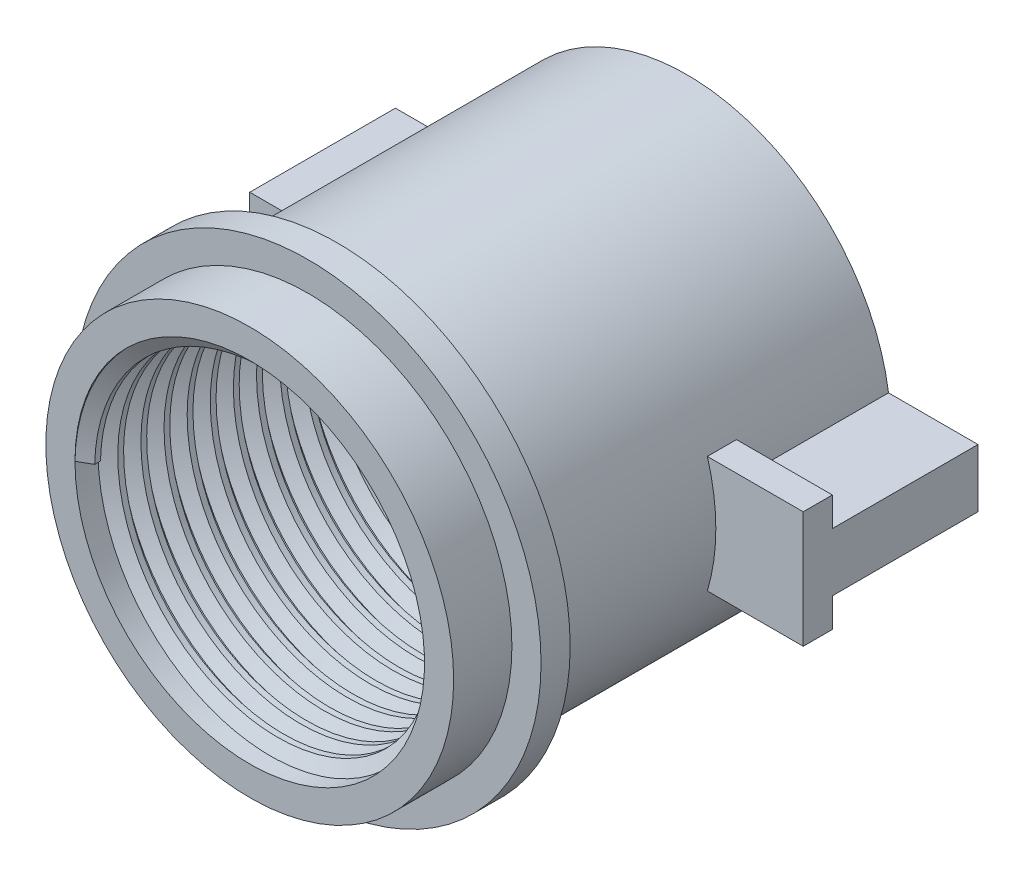
SolidWorks part; units mm, degrees
ref_plane "Plan de face" through (0, 0, 0) normal (0, 0, 1) x (1, 0, 0)
ref_plane "Plan de dessus" through (0, 0, 0) normal (0, 1, 0) x (1, 0, 0)
ref_plane "Plan de droite" through (0, 0, 0) normal (1, 0, 0) x (0, 0, -1)
sketch "Esquisse1" plane through (0, 0, 0) normal (0, 0, 1) x (1, 0, 0)
  circle A0 centre (0, 0) radius 7
extrude "Boss.-Extru.1" add sketch "Esquisse1" along normal blind 15
shell "Coque1" thickness 1 removed face at (7, 0, 15)
sketch "Esquisse2" plane through (0, 0, 0) normal (0, 0, -1) x (-1, 0, 0)
  circle A0 centre (0, 0) radius 2.75
extrude "Enlèv. mat.-Extru.1" cut sketch "Esquisse2" against normal blind 15
chamfer "Chanfrein1" distance 3 angle 45 1 edges at (6, 0, 1)
thread "Filetage1" pitch 0.7937 method extrude profile "Profil de filetage1" start angle 0, offset 0, length 8, pitch 0.7937, diameter 12
ref_plane "Plan1" through (-6, 0, 15) normal (0, -1, 0) x (-1, 0, 0)
sketch "Profil de filetage1" plane through (-6, 0, 15) normal (0, -1, 0) x (-1, 0, 0)
  line L0 (0, 0) -> (0, 0.7937) construction
  line L11 (0, 0) -> (0, 0.6945)
  line L12 (0, 0.6945) -> (-0.4296, 0.4465)
  line L13 (-0.4296, 0.4465) -> (-0.4296, 0.248)
  line L15 (-0.4296, 0.248) -> (0, 0)
  line L17 (-0.4296, 0.3473) -> (0, 0.3473) construction
  point P2 (0, 0)
  dimension "Pitch" = 0.7937
  dimension "Profile_Angle" = 60
  dimension "Profile_Land" = 0.1984
  dimension "Profile_Height" = 0.4296
sketch "Esquisse3" plane through (0, 0, 0) normal (0, 0, -1) x (-1, 0, 0)
  line L0 (0, 0) -> (-13.3501, 0) construction
  line L1 (-6.9282, 1) -> (-10, 1)
  line L2 (10, -1) -> (6.9282, -1)
  line L3 (10, -1) -> (10, 1)
  line L4 (10, 1) -> (6.9282, 1)
  line L5 (-10, -1) -> (-10, 1)
  line L6 (10, -1) -> (-10, 1) construction
  line L7 (10, 1) -> (-10, -1) construction
  line L8 (-6.9282, -1) -> (-10, -1)
  arc A0 (6.9282, -1) -> (6.9282, 1) centre (0, 0) ccw
  arc A1 (-6.9282, 1) -> (-6.9282, -1) centre (0, 0) ccw
  dimension "D1" = 20
  dimension "D2" = 2
extrude "Boss.-Extru.2" add sketch "Esquisse3" against normal blind 5
sketch "Esquisse4" plane through (0, 0, 5) normal (0, 0, 1) x (1, 0, 0)
  line L0 (10, 2) -> (10, -2)
  line L9 (11, -2) -> (11, 2)
  line L10 (11, 2) -> (5.6569, 2)
  line L11 (5.6569, -2) -> (11, -2)
  line L13 (10, 2) -> (6.7082, 2)
  line L14 (6.7082, -2) -> (10, -2)
  arc A0 (6.7082, 2) -> (6.7082, -2) centre (0, 0) cw
  circle A1 centre (0, 0) radius 7 construction
  arc A3 (5.6569, -2) -> (5.6569, 2) centre (0, 0) ccw
  dimension "D1" = 1
extrude "Boss.-Extru.3" add sketch "Esquisse4" along normal blind 1
sketch "Esquisse5" plane through (0, 0, 15) normal (0, 0, 1) x (1, 0, 0)
  circle A0 centre (0, 0) radius 7
  circle A1 centre (0, 0) radius 8
extrude "Boss.-Extru.4" add sketch "Esquisse5" against normal blind 1 from offset 2 offset against normal yes
